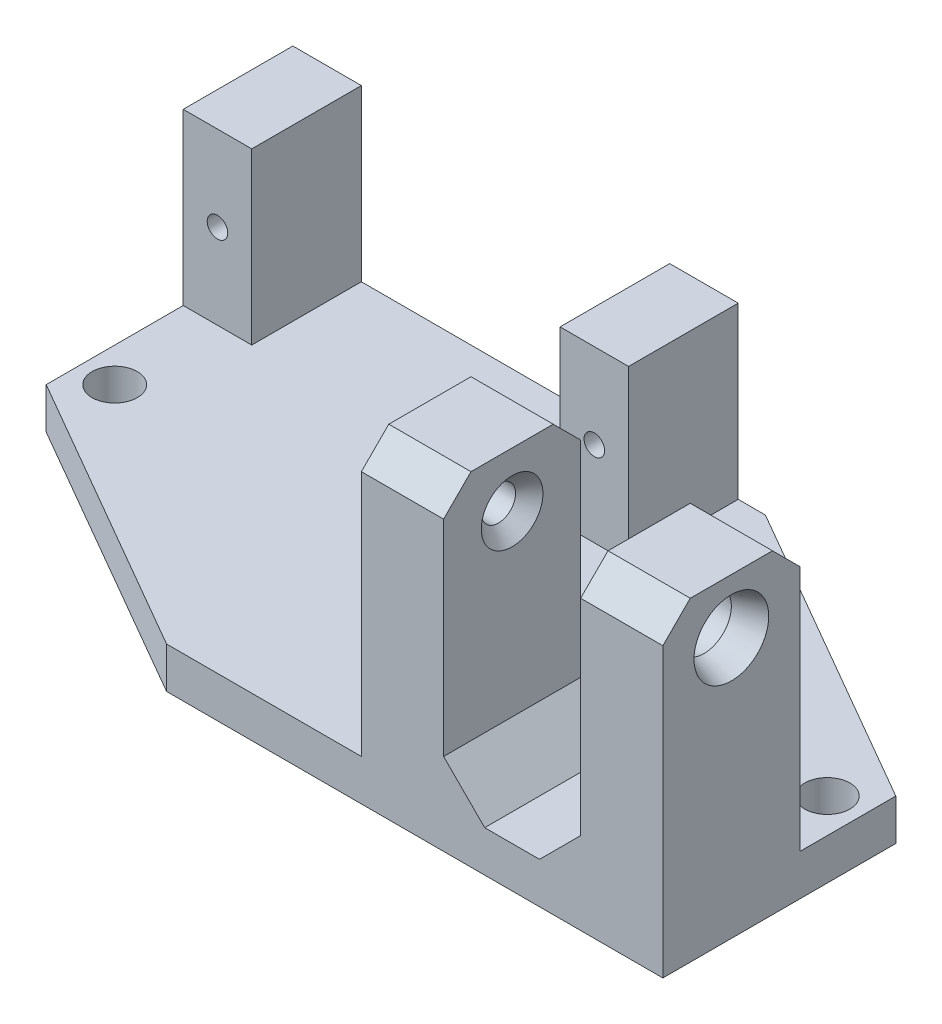
SolidWorks part; units mm, degrees
material "ABS PC"
ref_plane "Front Plane" through (0, 0, 0) normal (0, 0, 1) x (1, 0, 0)
ref_plane "Top Plane" through (0, 0, 0) normal (0, 1, 0) x (1, 0, 0)
ref_plane "Right Plane" through (0, 0, 0) normal (1, 0, 0) x (0, 0, -1)
sketch "Sketch1" plane through (0, 0, 0) normal (0, 1, 0) x (1, 0, 0)
  line L1 (-28.5, -18.5) -> (28.5, -18.5)
  line L2 (-28.5, -18.5) -> (-28.5, 18.5)
  line L3 (-28.5, 18.5) -> (28.5, 18.5)
  line L4 (28.5, -18.5) -> (28.5, 18.5)
  line L5 (-28.5, -18.5) -> (28.5, 18.5) construction
  line L6 (-28.5, 18.5) -> (28.5, -18.5) construction
  point P0 (0, 0)
  dimension "D1" = 57
  dimension "D2" = 37
extrude "Boss-Extrude1" add sketch "Sketch1" along normal blind 3
sketch "Sketch2" plane through (0, 3, 0) normal (0, 1, 0) x (1, 0, 0)
  line L0 (-28.5, 18.5) -> (-28.5, -18.5) construction
  line L1 (-28.5, 11.5) -> (-23.5, 11.5)
  line L2 (-28.5, 11.5) -> (-28.5, 3.5)
  line L3 (-28.5, 3.5) -> (-23.5, 3.5)
  line L4 (-23.5, 11.5) -> (-23.5, 3.5)
  line L5 (-28.5, -18.5) -> (28.5, -18.5) construction
  line L6 (-12.25, 18.5) -> (-12.25, -18.5) construction
  line L11 (28.5, 18.5) -> (-28.5, 18.5) construction
  line L12 (-1, 11.5) -> (-1, 3.5)
  line L13 (4, 3.5) -> (-1, 3.5)
  line L14 (4, 11.5) -> (4, 3.5)
  line L15 (4, 11.5) -> (-1, 11.5)
  dimension "D1" = 22
  dimension "D2" = 16.25
  dimension "D3" = 8
  dimension "D4" = 5
extrude "Boss-Extrude2" add sketch "Sketch2" along normal blind 12.4
hole_wizard "Ø1.5 (1.5) Diameter Hole1" positions "Sketch4" profile "Sketch5" hole size "Ø1.5" standard "ANSI Metric" end condition through all
sketch "Sketch4" plane through (0, 0, -3.5) normal (0, 0, 1) x (1, 0, 0)
  line L0 (-23.5, 9.2) -> (-1, 9.2) construction
  line L1 (-23.5, 15.4) -> (-23.5, 3) construction
  line L2 (-1, 15.4) -> (-1, 3) construction
  line L5 (-12.25, 9.2) -> (-12.25, 12.4109) construction
  line L6 (-26, 3) -> (-26, 9.2) construction
  line L7 (-28.5, 3) -> (-23.5, 3) construction
  point P16 (-26, 9.2)
  point P23 (1.5, 9.2)
  dimension "D1" = 6.2
sketch "Sketch5" plane through (1.5, 9.2, -3.5) normal (1, 0, 0) x (0, -1, 0)
  line L0 (0, 0) -> (0, 15)
  line L1 (0, 15) -> (0.75, 15)
  line L2 (0.75, 15) -> (0.75, 0)
  line L5 (0.75, 0) -> (0, 0)
  line L11 (0, -6.35) -> (0, 107.95) construction
  dimension "Thru Hole Dia." = 1.5
  dimension "Thru Hole Depth" = 15
sketch "Sketch6" plane through (0, 3, 0) normal (0, 1, 0) x (1, 0, 0)
  line L0 (-28.5, -18.5) -> (28.5, -18.5) construction
  line L1 (28.5, -18.5) -> (22.5, -18.5)
  line L2 (28.5, -18.5) -> (28.5, -8.5)
  line L3 (28.5, -8.5) -> (22.5, -8.5)
  line L4 (22.5, -18.5) -> (22.5, -8.5)
  line L5 (6.5, -18.5) -> (12.5, -18.5)
  line L6 (6.5, -18.5) -> (6.5, -8.5)
  line L7 (6.5, -8.5) -> (12.5, -8.5)
  line L8 (12.5, -18.5) -> (12.5, -8.5)
  dimension "D1" = 10
  dimension "D2" = 6
  dimension "D3" = 10
extrude "Boss-Extrude3" add sketch "Sketch6" along normal blind 20
sketch "Sketch7" plane through (28.5, 0, 0) normal (1, 0, 0) x (0, 0, -1)
  line L0 (-13.5, 23) -> (-13.5, 19) construction
  line L1 (-18.5, 23) -> (-8.5, 23) construction
  circle A0 centre (-13.5, 19) radius 2
  dimension "D1" = 4
  dimension "D2" = 4
extrude "Cut-Extrude1" cut sketch "Sketch7" against normal up to next
chamfer "Chamfer2" distance 2 angle 20 2 edges at (22.5, 19, 11.5) (28.5, 19, 11.5) first distance on face at (28.5, 19, 11.5)
chamfer "Chamfer3" distance 20 angle 60 1 edges at (28.5, 1.5, -18.5) first distance on face at (28.5, 19, 16.2279)
chamfer "Chamfer4" distance 12 angle 60 1 edges at (-28.5, 1.5, 18.5) first distance on face at (-28.5, 5.35, -3.75)
hole_wizard "Ø3.3 (3.3) Diameter Hole1" positions "Sketch8" profile "Sketch9" hole size "Ø3.3" standard "ANSI Metric" end condition through all
sketch "Sketch8" plane through (0, 3, 0) normal (0, 1, 0) x (1, 0, 0)
  point P0 (26, -4)
  point P3 (-26, -4)
sketch "Sketch9" plane through (26, 3, 4) normal (1, 0, 0) x (0, 0, 1)
  line L0 (0, 0) -> (0, 3)
  line L1 (0, 3) -> (1.65, 3)
  line L2 (1.65, 3) -> (1.65, 0)
  line L5 (1.65, 0) -> (0, 0)
  line L11 (0, -6.35) -> (0, 107.95) construction
  dimension "Thru Hole Dia." = 3.3
  dimension "Thru Hole Depth" = 3
chamfer "Chamfer5" distance 3 angle 45 2 edges at (22.5, 3, 13.5) (12.5, 3, 13.5)
sketch "Sketch10" plane through (0, 3, 0) normal (0, 1, 0) x (1, 0, 0)
  line L0 (12.0357, 5.1189) -> (16.3659, 2.6189)
  line L1 (12.0357, 5.1189) -> (11.0357, 3.3868)
  line L2 (16.3659, 2.6189) -> (15.3659, 0.8868)
  line L3 (11.0357, 3.3868) -> (15.3659, 0.8868)
  line L4 (28.5, -1.5) -> (-6.141, 18.5) construction
  line L5 (8.7747, 2.9602) -> (16.388, -1.4353) construction
  line L6 (9.5357, 0.7888) -> (13.8659, -1.7112)
  line L7 (12.8659, -3.4433) -> (13.8659, -1.7112)
  line L8 (8.5357, -0.9433) -> (9.5357, 0.7888)
  line L9 (8.5357, -0.9433) -> (12.8659, -3.4433)
  dimension "D1" = 2
  dimension "D2" = 5
  dimension "D3" = 2.5
  dimension "D4" = 3
extrude "Cut-Extrude2" [suppressed] cut sketch "Sketch10" against normal through all
sketch "Sketch11" plane through (0, 0, 18.5) normal (0, 0, 1) x (1, 0, 0)
  line L0 (1.5, 9.2) -> (10, 9.2) construction
  line L1 (10, 9.2) -> (6.5, 12.7)
  line L2 (6.5, 23) -> (6.5, 3) construction
  line L3 (6.5, 12.7) -> (6.5, 5.7)
  line L4 (10, 9.2) -> (6.5, 5.7)
  dimension "D1" = 7
extrude "Cut-Extrude3" [suppressed] cut sketch "Sketch11" against normal up to next
sketch "Sketch12" plane through (0, 3, 0) normal (0, 1, 0) x (1, 0, 0)
  line L0 (28.5, -1.5) -> (-6.141, 18.5) construction
  line L1 (-28.5, 18.5) -> (5.9833, 18.5)
  line L2 (-28.5, 18.5) -> (-28.5, 11.5)
  line L3 (-28.5, 11.5) -> (5.9833, 11.5)
  line L4 (5.9833, 18.5) -> (5.9833, 11.5)
  line L5 (4, 11.5) -> (-1, 11.5) construction
extrude "Cut-Extrude4" cut sketch "Sketch12" against normal blind 10
chamfer "Chamfer6" distance 2 angle 45 4 edges at (25.5, 23, 18.5) (25.5, 23, 8.5) (9.5, 23, 8.5) (9.5, 23, 18.5)
sketch "Sketch13" plane through (6.5, 0, 0) normal (-1, 0, 0) x (0, 0, 1)
  circle A0 centre (13.5, 19) radius 1.25
  dimension "D1" = 2.5
extrude "Cut-Extrude5" cut sketch "Sketch13" against normal up to next
chamfer "Chamfer7" distance 1 angle 45 2 edges at (12.5, 19, 14.75) (6.5, 19, 14.75)
